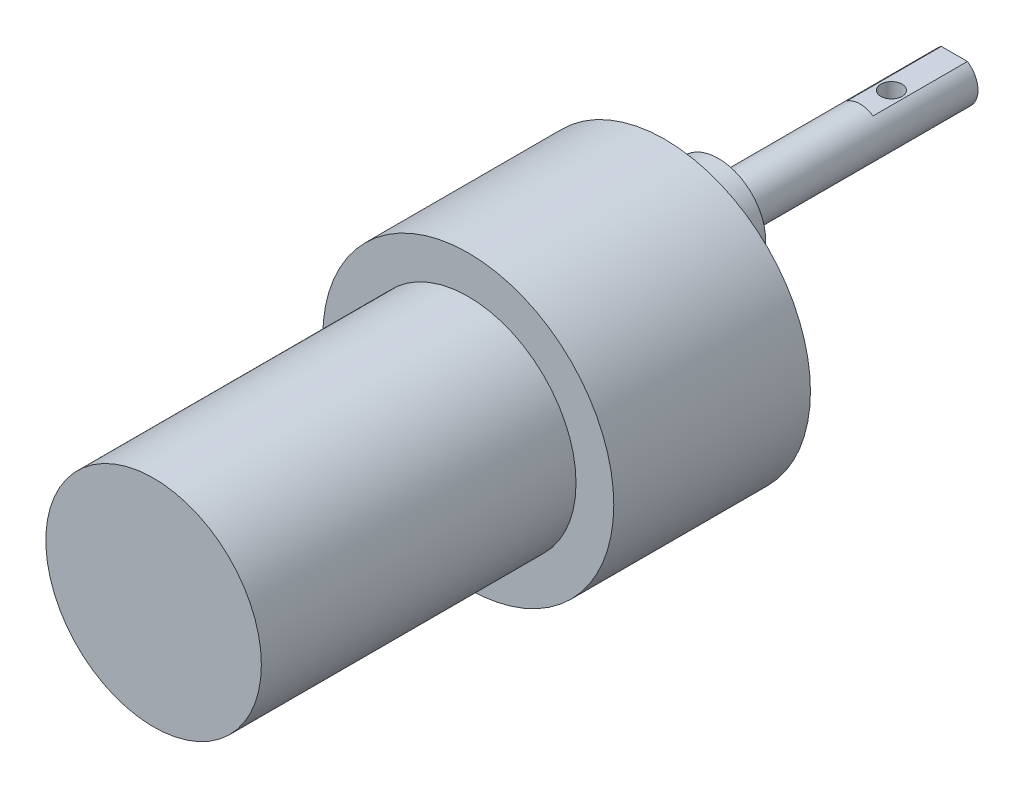
SolidWorks part; units mm, degrees
material "Plain Carbon Steel"
ref_plane "Front Plane" through (0, 0, 0) normal (0, 0, 1) x (1, 0, 0)
ref_plane "Top Plane" through (0, 0, 0) normal (0, 1, 0) x (1, 0, 0)
ref_plane "Right Plane" through (0, 0, 0) normal (1, 0, 0) x (0, 0, -1)
sketch "Sketch1" plane through (0, 0, 0) normal (0, 0, 1) x (1, 0, 0)
  circle A0 centre (0, 0) radius 18.5
  dimension "D1" = 37
extrude "Boss-Extrude1" add sketch "Sketch1" along normal blind 25
sketch "Sketch2" plane through (0, 0, 0) normal (0, 0, -1) x (-1, 0, 0)
  circle A0 centre (0, 7) radius 6
  dimension "D1" = 12
  dimension "D2" = 7
extrude "Boss-Extrude2" add sketch "Sketch2" along normal blind 6.8
sketch "Sketch3" plane through (0, 0, -6.8) normal (0, 0, -1) x (-1, 0, 0)
  circle A0 centre (0, 7) radius 3
extrude "Boss-Extrude3" add sketch "Sketch3" along normal blind 30
sketch "Sketch4" plane through (0, 0, -36.8) normal (0, 0, -1) x (-1, 0, 0)
  line L0 (-1.6583, 9.5) -> (1.6583, 9.5)
  circle A0 centre (0, 7) radius 3
  circle M2 centre (0, 7) radius 3
  dimension "D1" = 2.5
  dimension "D2" = 6
extrude "Cut-Extrude1" cut sketch "Sketch4" against normal blind 12 contours L0 M2 region at (0, 9.7015, -36.8)
sketch "Sketch5" plane through (0, 0, 25) normal (0, 0, 1) x (1, 0, 0)
  circle A0 centre (0, 0) radius 13.7
  dimension "D1" = 27.4
extrude "Boss-Extrude4" add sketch "Sketch5" along normal blind 40
sketch "Sketch6" plane through (0, 0, 0) normal (0, 0, -1) x (-1, 0, 0)
  line L0 (0, 7) -> (0, 0) construction
  line L1 (0, 0) -> (-15.75, 0) construction
  circle A0 centre (0, 0) radius 15.75 construction
  circle A1 centre (-15.75, 0) radius 1.5
  circle A2 centre (-7.875, 13.6399) radius 1.5
  circle A3 centre (7.875, 13.6399) radius 1.5
  circle A4 centre (15.75, 0) radius 1.5
  circle A5 centre (7.875, -13.6399) radius 1.5
  circle A6 centre (-7.875, -13.6399) radius 1.5
  point P19 (0, 0)
  dimension "D1" = 31.5
  dimension "D2" = 3
  dimension "D3" = 6
extrude "Cut-Extrude2" cut sketch "Sketch6" against normal blind 3.2
thread "Thread1" pitch 1.0583 method extrude profile "Thread Profile1" start angle 0, offset 0, length 3.2, pitch 1.0583, diameter 3
ref_plane "Plane1" through (17.25, 0, 0) normal (0, -1, 0) x (1, 0, 0)
sketch "Thread Profile1" plane through (17.25, 0, 0) normal (0, -1, 0) x (1, 0, 0)
  line L0 (0, 0) -> (0, 1.0583) construction
  line L11 (0, 0) -> (0, 0.926)
  line L12 (0, 0.926) -> (-0.5728, 0.5953)
  line L13 (-0.5728, 0.5953) -> (-0.5728, 0.3307)
  line L15 (-0.5728, 0.3307) -> (0, 0)
  line L17 (-0.5728, 0.463) -> (0, 0.463) construction
  point P2 (0, 0)
  dimension "Pitch" = 1.0583
  dimension "Profile_Angle" = 60
  dimension "Profile_Land" = 0.2646
  dimension "Profile_Height" = 0.5728
sketch "Sketch7" plane through (0, 9.5, 0) normal (0, 1, 0) x (1, 0, 0)
  line L0 (1.6583, 36.8) -> (-1.6583, 36.8) construction
  circle A0 centre (0, 28.8) radius 1.3505
  dimension "D1" = 8
extrude "Cut-Extrude3" cut sketch "Sketch7" against normal blind 10
sketch "Sketch8" plane through (0, 0, 0) normal (0, 0, -1) x (-1, 0, 0)
  line L0 (-6, 7) -> (6, 7) construction
  circle A0 centre (0, 7) radius 6 construction
  circle A1 centre (0, 7) radius 6 construction
